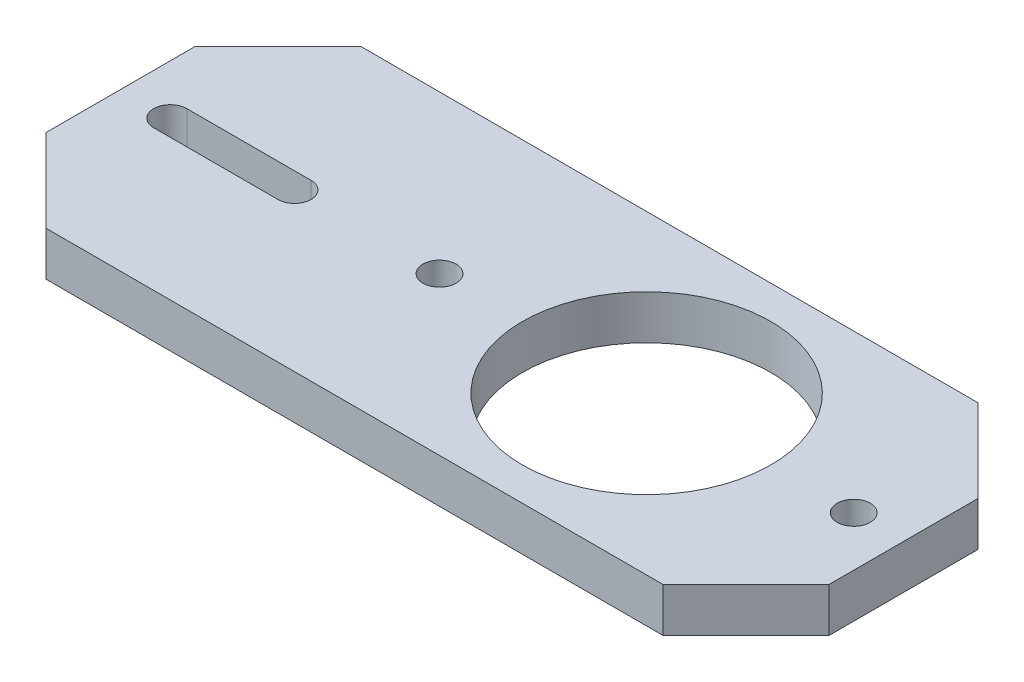
SolidWorks part; units mm, degrees
material "Pine"
ref_plane "Front Plane" through (0, 0, 0) normal (0, 0, 1) x (1, 0, 0)
ref_plane "Top Plane" through (0, 0, 0) normal (0, 1, 0) x (1, 0, 0)
ref_plane "Right Plane" through (0, 0, 0) normal (1, 0, 0) x (0, 0, -1)
sketch "Sketch1" plane through (0, 0, 0) normal (0, 1, 0) x (1, 0, 0)
  line L0 (-57.5, 2) -> (-42.5, 2)
  line L1 (-57.5, -2) -> (-42.5, -2)
  line L2 (-84.5376, 0) -> (67.9764, 0) construction
  line L3 (-50, 2) -> (-50, -2) construction
  line L4 (-63.5, 9) -> (-53.5, 19)
  line L5 (-53.5, 19) -> (21, 19)
  line L6 (-63.5, 9) -> (-63.5, -9)
  line L7 (-53.5, -19) -> (21, -19)
  line L8 (31, 9) -> (31, -9)
  line L9 (-63.5, -9) -> (-53.5, -19)
  line L10 (21, -19) -> (31, -9)
  line L11 (21, 19) -> (31, 9)
  circle A0 centre (-25, 0) radius 2
  circle A1 centre (25, 0) radius 2
  arc A2 (-42.5, -2) -> (-42.5, 2) centre (-42.5, 0) ccw
  arc A4 (-57.5, 2) -> (-57.5, -2) centre (-57.5, 0) ccw
  circle A5 centre (0, 0) radius 15
  point P19 (-63.5, 19)
  point P20 (31, -19)
  point P21 (-63.5, -19)
  point P22 (31, 19)
  dimension "D1" = 4
  dimension "D2" = 4
  dimension "D4" = 4
  dimension "D5" = 75
  dimension "D8" = 4
  dimension "D10" = 30
  dimension "D12" = 6
  dimension "D3" = 50
  dimension "D6" = 15
  dimension "D7" = 6
  dimension "D11" = 25
  dimension "D14" = 19
  dimension "D15" = 19
extrude "Boss-Extrude1" add sketch "Sketch1" against normal blind 5.333
equation "\"rod_diameter\"= 8"
equation "\"rod_hole_thickness\"= 4"
equation "\"rod_radius\"= \"rod_diameter\" / 2"
equation "\"platter_diameter\"= 320"
equation "\"platter_radius\"= \"platter_diameter\" / 2"
equation "\"extruder_mount_hole_spacing\"= 75"
equation "\"arm_rod_spacing\"= 40"
equation "\"motor_level_rod_spacing\"= 15"
equation "\"linear_bearing_diameter\"= 15"
equation "\"z_rod_spacing\"= 75"
equation "\"platter_rod_spacing\"= 50"
equation "\"rod_nut_thickness\"= 6.5"
equation "\"rod_nut_inscribed_diameter\"= 13"
equation "\"z_height\"= 350"
equation "\"gear_pitch\"=2"
equation "\"r_gear_teeth\"= 450"
equation "\"theta_gear_teeth\"= 385"
equation "\"D12@Sketch1\"=2 + \"rod_hole_thickness\""
equation "\"D14@Sketch1\"=15 +\"rod_hole_thickness\""
equation "\"D15@Sketch1\" = 15 + \"rod_hole_thickness\""
equation "\"D7@Sketch1\"=\"rod_hole_thickness\"+2"
equation "\"D5@Sketch1\"=\"extruder_mount_hole_spacing\""
equation "\"top_frame_spacing\"= 90"
equation "\"z_drive_rod_offset\"= 12"
equation "\"sheet_thickness\"=5.333"
equation "\"sheet_tab_hole_thickness\"= \"sheet_thickness\""
equation "\"sheet_tab_width\"= \"sheet_thickness\"*2"
equation "\"sheet_double_tab_width\"= 35"
equation "\"sheet_bolt_diameter\"= 3"
equation "\"sheet_bolt_length\"= 16"
equation "\"sheet_nut_diameter\"= 5.5"
equation "\"sheet_nut_thickness\"= 2.5"
equation "\"sheet_nut_depth\"= 10"
equation "\"bearing_outside_diameter\"= 22"
equation "\"bearing_thickness\"= 7"
equation "\"corner_part_thickness\"= \"sheet_thickness\" + \"bearing_thickness\""
equation "\"setscrew_nut_diameter\"= 6"
equation "\"setscrew_nut_thickness\"= 3"
equation "\"setscrew_bolt_diameter\"= 3"
equation "\"motor_shaft_diameter\"= 5.7"
equation "\"D1@Boss-Extrude1\"= \"sheet_thickness\""
